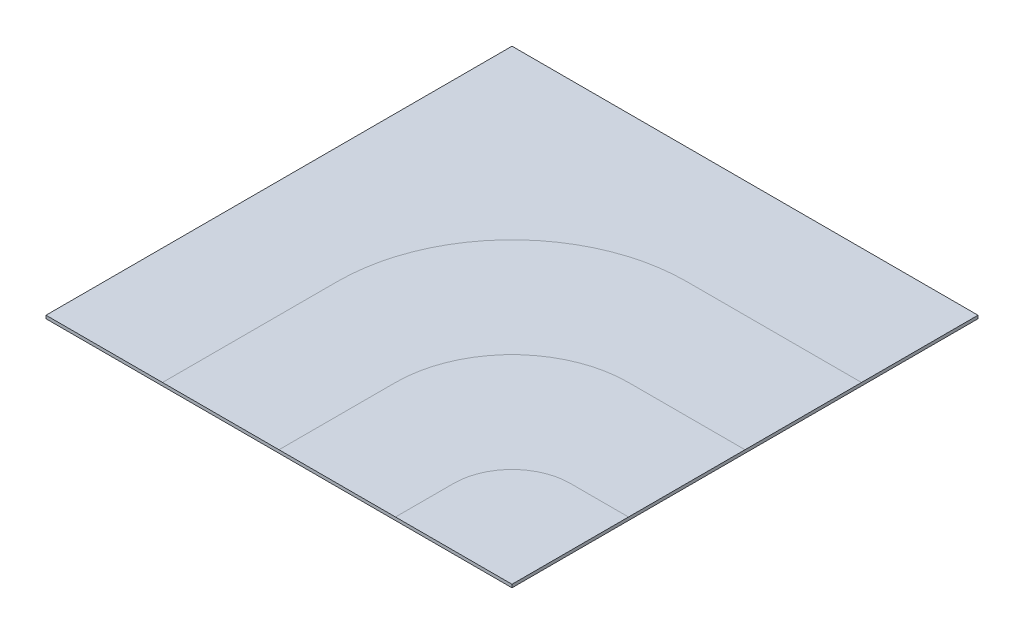
SolidWorks part; units mm, degrees
ref_plane "Front Plane" through (0, 0, 0) normal (0, 0, 1) x (1, 0, 0)
ref_plane "Top Plane" through (0, 0, 0) normal (0, 1, 0) x (1, 0, 0)
ref_plane "Right Plane" through (0, 0, 0) normal (1, 0, 0) x (0, 0, -1)
sketch "Sketch2" plane through (0, 0, 0) normal (0, 1, 0) x (1, 0, 0)
  line L0 (375, 0) -> (375, 562.5)
  line L1 (0, 0) -> (1500, 0)
  line L2 (0, 0) -> (0, 1500)
  line L3 (0, 1500) -> (1500, 1500)
  line L4 (1500, 0) -> (1500, 1500)
  line L5 (937.5, 1125) -> (1500, 1125)
  line L6 (1125, 0) -> (1125, 187.5)
  line L7 (1312.5, 375) -> (1500, 375)
  arc A3 (937.5, 1125) -> (375, 562.5) centre (937.5, 562.5) ccw
  arc A4 (1312.5, 375) -> (1125, 187.5) centre (1312.5, 187.5) ccw
  dimension "D1" = 1500
  dimension "D2" = 1500
  dimension "D3" = 375
  dimension "D5" = 375
extrude "Boss-Extrude2" add sketch "Sketch2" along normal blind 10 contours A3 L5 L4 L3 L2 L1 L0 | A4 L7 L4 L5 A3 L0 L1 L6 | L7 A4 L6 L1 L4 region at (508.394, 0, -991.606) region at (917.4551, 0, -582.5449) region at (1320.7554, 0, -179.2446)
sketch "Sketch3" plane through (0, 10, 0) normal (0, 1, 0) x (1, 0, 0)
  line L0 (750, 0) -> (750, 375)
  line L1 (0, 0) -> (1500, 0) construction
  line L2 (1125, 750) -> (1500, 750)
  arc A0 (1125, 750) -> (750, 375) centre (1125, 375) ccw
split line "Split Line2"
split line "Split Line6"
sketch "Sketch2<16>" plane through (0, 0, 0) normal (0, 1, 0) x (1, 0, 0) same geometry as "Sketch2"
split line "Split Line7"
sketch "Sketch2<17>" plane through (0, 0, 0) normal (0, 1, 0) x (1, 0, 0) same geometry as "Sketch2"
equation "\"Scale\"= 8"
equation "\"Tile Size\"= \"Road Size\" * 2"
equation "\"Road Size\"= \"Real Lane Size\" * 2 / \"Scale\""
equation "\"Real Lane Size\"= 3m"
